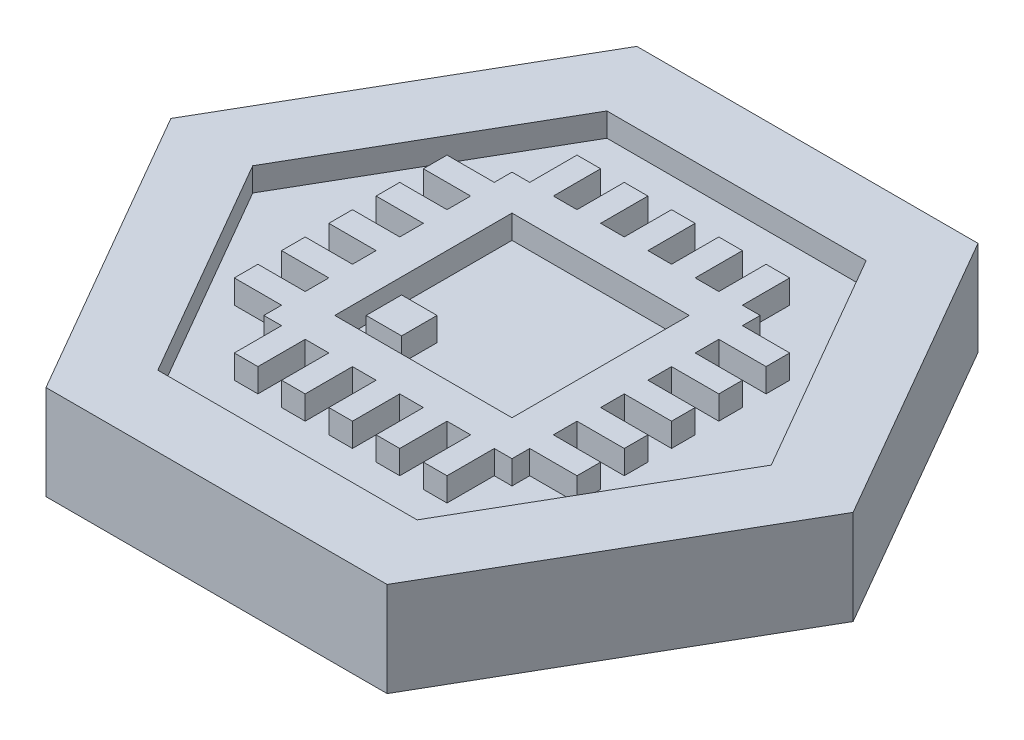
SolidWorks part; units mm, degrees
ref_plane "前视基准面" through (0, 0, 0) normal (0, 0, 1) x (1, 0, 0)
ref_plane "上视基准面" through (0, 0, 0) normal (0, 1, 0) x (1, 0, 0)
ref_plane "右视基准面" through (0, 0, 0) normal (1, 0, 0) x (0, 0, -1)
sketch "草图1" plane through (0, 0, 0) normal (0, 1, 0) x (1, 0, 0)
  line L1 (14.4338, 0) -> (7.2169, 12.5)
  line L2 (7.2169, 12.5) -> (-7.2169, 12.5)
  line L3 (-7.2169, 12.5) -> (-14.4338, 0)
  line L4 (-14.4338, 0) -> (-7.2169, -12.5)
  line L5 (-7.2169, -12.5) -> (7.2169, -12.5)
  line L6 (7.2169, -12.5) -> (14.4338, 0)
  circle A0 centre (0, 0) radius 12.5 construction
  dimension "D1" = 25
extrude "凸台-拉伸1" add sketch "草图1" along normal blind 4
sketch "草图2" plane through (0, 4, 0) normal (0, 1, 0) x (1, 0, 0)
  line L0 (5.4848, -9.5) -> (10.9697, 0)
  line L1 (10.9697, 0) -> (5.4848, 9.5)
  line L2 (5.4848, 9.5) -> (-5.4848, 9.5)
  line L3 (-5.4848, 9.5) -> (-10.9697, 0)
  line L4 (-10.9697, 0) -> (-5.4848, -9.5)
  line L5 (-5.4848, -9.5) -> (5.4848, -9.5)
  line L6 (7.2169, -12.5) -> (14.4338, 0)
  line L7 (14.4338, 0) -> (7.2169, 12.5)
  line L8 (7.2169, 12.5) -> (-7.2169, 12.5)
  line L9 (-7.2169, 12.5) -> (-14.4338, 0)
  line L10 (-14.4338, 0) -> (-7.2169, -12.5)
  line L11 (-7.2169, -12.5) -> (7.2169, -12.5)
  line L12 (7.2169, -12.5) -> (14.4338, 0)
  line L13 (14.4338, 0) -> (7.2169, 12.5)
  line L14 (7.2169, 12.5) -> (-7.2169, 12.5)
  line L15 (-7.2169, 12.5) -> (-14.4338, 0)
  line L16 (-14.4338, 0) -> (-7.2169, -12.5)
  line L17 (-7.2169, -12.5) -> (7.2169, -12.5)
  dimension "D1" = 0
  dimension "D2" = 3
extrude "切除-拉伸1" cut sketch "草图2" against normal blind 1 contours L0 L1 L2 L3 L4 L5
sketch "草图3" plane through (0, 3, 0) normal (0, 1, 0) x (1, 0, 0)
  line L20 (5.25, -4.5) -> (7.25, -4.5)
  line L21 (5.25, 5.25) -> (-5.25, 5.25)
  line L22 (5.25, 5.25) -> (5.25, -5.25)
  line L23 (5.25, -5.25) -> (-5.25, -5.25)
  line L24 (-5.25, 5.25) -> (-5.25, -5.25)
  line L25 (5.25, 5.25) -> (-5.25, -5.25) construction
  line L26 (5.25, -5.25) -> (-5.25, 5.25) construction
  line L27 (5.25, -4.5) -> (5.25, -3.5)
  line L28 (7.25, -4.5) -> (7.25, -3.5)
  line L29 (5.25, -3.5) -> (7.25, -3.5)
  line L30 (5.25, -2.5) -> (7.25, -2.5)
  line L31 (5.25, -2.5) -> (5.25, -1.5)
  line L32 (7.25, -2.5) -> (7.25, -1.5)
  line L33 (5.25, -1.5) -> (7.25, -1.5)
  line L34 (5.25, -0.5) -> (7.25, -0.5)
  line L35 (5.25, -0.5) -> (5.25, 0.5)
  line L36 (7.25, -0.5) -> (7.25, 0.5)
  line L37 (5.25, 0.5) -> (7.25, 0.5)
  line L38 (5.25, 1.5) -> (7.25, 1.5)
  line L39 (5.25, 1.5) -> (5.25, 2.5)
  line L40 (7.25, 1.5) -> (7.25, 2.5)
  line L41 (5.25, 2.5) -> (7.25, 2.5)
  line L42 (5.25, 3.5) -> (7.25, 3.5)
  line L43 (5.25, 3.5) -> (5.25, 4.5)
  line L44 (7.25, 3.5) -> (7.25, 4.5)
  line L45 (5.25, 4.5) -> (7.25, 4.5)
  line L46 (0, -5.25) -> (0, 5.25) construction
  line L47 (0, 5.25) -> (-5.25, 0) construction
  line L48 (-5.25, 0) -> (5.25, 0) construction
  line L49 (-5.25, 4.5) -> (-7.25, 4.5)
  line L50 (-7.25, 3.5) -> (-7.25, 4.5)
  line L51 (-5.25, 3.5) -> (-5.25, 4.5)
  line L52 (-5.25, 3.5) -> (-7.25, 3.5)
  line L53 (-5.25, 2.5) -> (-7.25, 2.5)
  line L54 (-7.25, 1.5) -> (-7.25, 2.5)
  line L55 (-5.25, 1.5) -> (-5.25, 2.5)
  line L56 (-5.25, 1.5) -> (-7.25, 1.5)
  line L57 (-5.25, 0.5) -> (-7.25, 0.5)
  line L58 (-7.25, -0.5) -> (-7.25, 0.5)
  line L59 (-5.25, -0.5) -> (-5.25, 0.5)
  line L60 (-5.25, -0.5) -> (-7.25, -0.5)
  line L61 (-5.25, -1.5) -> (-7.25, -1.5)
  line L62 (-7.25, -2.5) -> (-7.25, -1.5)
  line L63 (-5.25, -2.5) -> (-5.25, -1.5)
  line L64 (-5.25, -2.5) -> (-7.25, -2.5)
  line L65 (-5.25, -3.5) -> (-7.25, -3.5)
  line L66 (-7.25, -4.5) -> (-7.25, -3.5)
  line L67 (-5.25, -4.5) -> (-5.25, -3.5)
  line L68 (-5.25, -4.5) -> (-7.25, -4.5)
  line L69 (4.5, -5.25) -> (4.5, -7.25)
  line L70 (4.5, -5.25) -> (3.5, -5.25)
  line L71 (4.5, -7.25) -> (3.5, -7.25)
  line L72 (3.5, -5.25) -> (3.5, -7.25)
  line L73 (2.5, -5.25) -> (2.5, -7.25)
  line L74 (2.5, -5.25) -> (1.5, -5.25)
  line L75 (2.5, -7.25) -> (1.5, -7.25)
  line L76 (1.5, -5.25) -> (1.5, -7.25)
  line L77 (0.5, -5.25) -> (0.5, -7.25)
  line L78 (0.5, -5.25) -> (-0.5, -5.25)
  line L79 (0.5, -7.25) -> (-0.5, -7.25)
  line L80 (-0.5, -5.25) -> (-0.5, -7.25)
  line L81 (-1.5, -5.25) -> (-1.5, -7.25)
  line L82 (-1.5, -5.25) -> (-2.5, -5.25)
  line L83 (-1.5, -7.25) -> (-2.5, -7.25)
  line L84 (-2.5, -5.25) -> (-2.5, -7.25)
  line L85 (-3.5, -5.25) -> (-3.5, -7.25)
  line L86 (-3.5, -5.25) -> (-4.5, -5.25)
  line L87 (-3.5, -7.25) -> (-4.5, -7.25)
  line L88 (-4.5, -5.25) -> (-4.5, -7.25)
  line L89 (-4.5, 5.25) -> (-4.5, 7.25)
  line L90 (-3.5, 7.25) -> (-4.5, 7.25)
  line L91 (-3.5, 5.25) -> (-4.5, 5.25)
  line L92 (-3.5, 5.25) -> (-3.5, 7.25)
  line L93 (-2.5, 5.25) -> (-2.5, 7.25)
  line L94 (-1.5, 7.25) -> (-2.5, 7.25)
  line L95 (-1.5, 5.25) -> (-2.5, 5.25)
  line L96 (-1.5, 5.25) -> (-1.5, 7.25)
  line L97 (-0.5, 5.25) -> (-0.5, 7.25)
  line L98 (0.5, 7.25) -> (-0.5, 7.25)
  line L99 (0.5, 5.25) -> (-0.5, 5.25)
  line L100 (0.5, 5.25) -> (0.5, 7.25)
  line L101 (1.5, 5.25) -> (1.5, 7.25)
  line L102 (2.5, 7.25) -> (1.5, 7.25)
  line L103 (2.5, 5.25) -> (1.5, 5.25)
  line L104 (2.5, 5.25) -> (2.5, 7.25)
  line L105 (3.5, 5.25) -> (3.5, 7.25)
  line L106 (4.5, 7.25) -> (3.5, 7.25)
  line L107 (4.5, 5.25) -> (3.5, 5.25)
  line L108 (4.5, 5.25) -> (4.5, 7.25)
  line L110 (3.75, 3.75) -> (-3.75, 3.75)
  line L111 (3.75, 3.75) -> (3.75, -3.75)
  line L112 (3.75, -3.75) -> (-3.75, -3.75)
  line L113 (-3.75, 3.75) -> (-3.75, -3.75)
  line L114 (3.75, 3.75) -> (-3.75, -3.75) construction
  line L115 (3.75, -3.75) -> (-3.75, 3.75) construction
  point P0 (0, 0)
  point P16 (0, 0)
  dimension "D1" = 5
  dimension "D7" = 2
  dimension "D2" = 2
  dimension "D3" = 1
  dimension "D4" = 10.5
  dimension "D6" = 1
  dimension "D8" = 0.5
  dimension "D9" = 0.5
  dimension "D10" = 1.5
  dimension "D5" = 5
extrude "凸台-拉伸2" add sketch "草图3" along normal blind 1 contours L21 L24 L23 L22 | L37 L22 L34 L36 | L29 L22 L20 L28 | L23 L72 L71 L69 | L23 L76 L75 L73 | L23 L84 L83 L81 | L68 L24 L65 L66 | L60 L24 L57 L58 | L52 L24 L49 L50 | L21 L92 L90 L89 | L21 L96 L94 L93 | L21 L100 L98 L97 | L21 L108 L106 L105 | L41 L22 L38 L40 | L33 L32 L30 L31 | L77 L79 L80 L78 | L85 L87 L88 L86 | L64 L62 L61 L63 | L56 L54 L53 L55 | L104 L102 L101 L103 | L45 L44 L42 L43 region at (6.25, 3, 4) region at (5.1015, 3, 4.875) region at (4, 3, 6.25) region at (6.25, 3, 0) region at (2, 3, 6.25) region at (6.25, 3, -2) region at (-2, 3, 6.25) region at (4, 3, -6.25) region at (-6.25, 3, 4) region at (0, 3, -6.25) region at (-2, 3, -6.25) region at (-6.25, 3, 0) region at (-4, 3, -6.25) region at (-6.25, 3, -4)
sketch "草图4" plane through (0, 3, 0) normal (0, 1, 0) x (1, 0, 0)
  line L0 (-3.75, -3.75) -> (-2.3358, -2.3358) construction
  line L1 (-3.75, 3.75) -> (-3.75, -3.75) construction
  line L3 (-3.0858, -3.0858) -> (-1.5858, -3.0858)
  line L4 (-3.0858, -3.0858) -> (-3.0858, -1.5858)
  line L5 (-3.0858, -1.5858) -> (-1.5858, -1.5858)
  line L6 (-1.5858, -3.0858) -> (-1.5858, -1.5858)
  line L7 (-3.0858, -3.0858) -> (-1.5858, -1.5858) construction
  line L8 (-3.0858, -1.5858) -> (-1.5858, -3.0858) construction
  dimension "D2" = 1.5
  dimension "D1" = 2
  dimension "D3" = 135
extrude "凸台-拉伸3" add sketch "草图4" along normal blind 1
